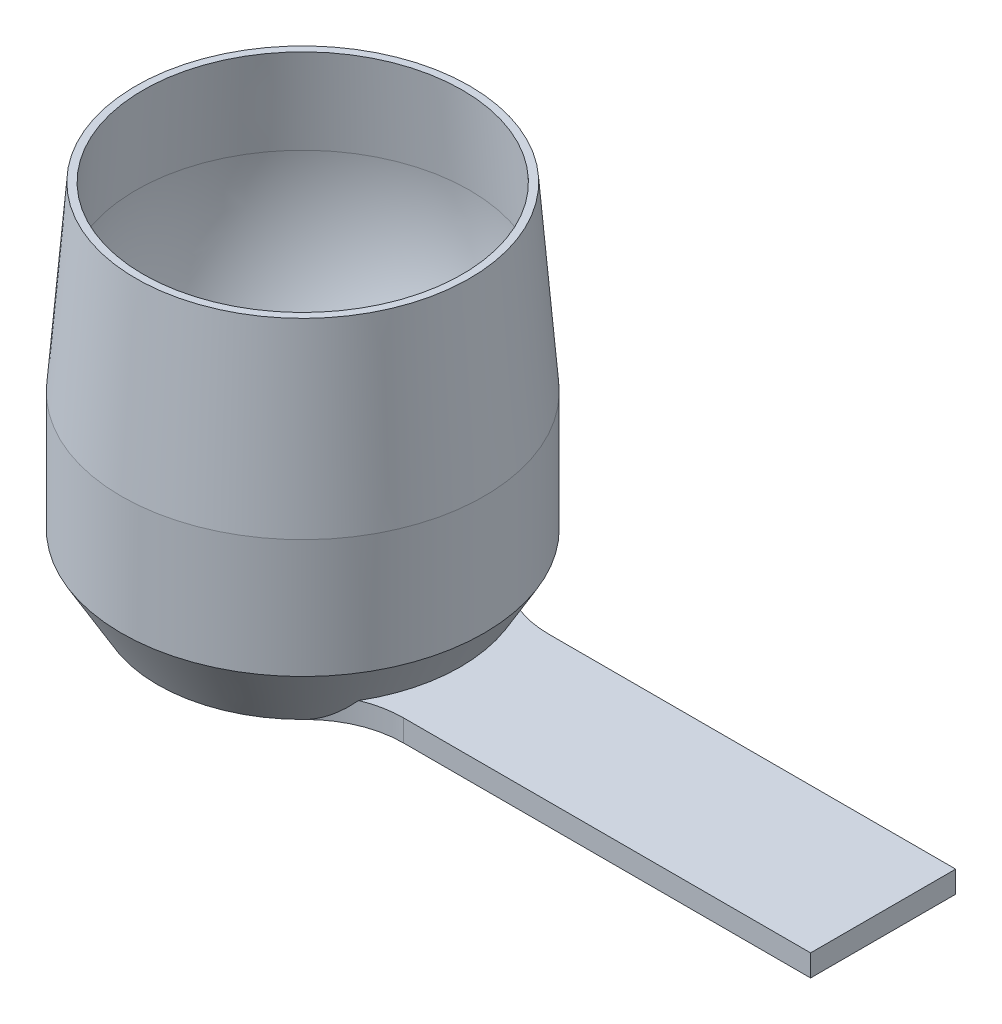
SolidWorks part; units mm, degrees
ref_plane "Front Plane" through (0, 0, 0) normal (0, 0, 1) x (1, 0, 0)
ref_plane "Top Plane" through (0, 0, 0) normal (0, 1, 0) x (1, 0, 0)
ref_plane "Right Plane" through (0, 0, 0) normal (1, 0, 0) x (0, 0, -1)
sketch "Sketch6" plane through (0, 0, 0) normal (1, 0, 0) x (0, 0, -1)
  line L0 (0, 0.6285) -> (0, 26.7591) construction
  line L1 (0, 0) -> (-20, 0)
  line L2 (-25, 8.6603) -> (-25, 25)
  line L3 (-25, 25) -> (-23, 50)
  line L4 (-23, 50) -> (-22, 50)
  line L5 (-22, 50) -> (-22.9959, 37.5511)
  line L7 (0, 0.8) -> (0, 0)
  line L8 (-25, 8.6603) -> (-20, 0)
  line L9 (-2, 0.8) -> (0, 0.8)
  spline S0 degree 3 poles (-22.9959, 37.5511) (-24.2566, 21.792) (-15.3927, 8.1158) (-2, 0.8) knots 0 0 0 0 1 1 1 1
  point P4 (-17.152, 14.4825)
  point P9 (-9.1762, 5.4384)
  point P14 (-17.7495, 15.6038)
  dimension "D1" = 50
  dimension "D2" = 46
  dimension "D3" = 25
  dimension "D4" = 50
  dimension "D5" = 30
  dimension "D6" = 1
  dimension "D7" = 2
  dimension "D8" = 0.8
  dimension "D9" = 10
  dimension "D10" = 40
revolve "Revolve1" add sketch "Sketch6" angle 360 about L0
sketch "Sketch7" plane through (0, 0, 0) normal (0, 1, 0) x (1, 0, 0)
  line L1 (23.8874, -10) -> (80, -10)
  line L6 (23.8874, 10) -> (80, 10)
  line L7 (80, -10) -> (80, 10)
  arc A8 (23.8874, -10) -> (14.2482, -14.0353) centre (23.8874, -23.5305) ccw
  circle A9 centre (0, 0) radius 20
  arc A10 (14.2482, -14.0353) -> (14.2482, 14.0353) centre (0, 0) ccw
  arc A11 (14.2482, 14.0353) -> (23.8874, 10) centre (23.8874, 23.5305) ccw
  dimension "D1" = 0
  dimension "D2" = 20
  dimension "D3" = 80
extrude "Boss-Extrude2" add sketch "Sketch7" along normal blind 3
